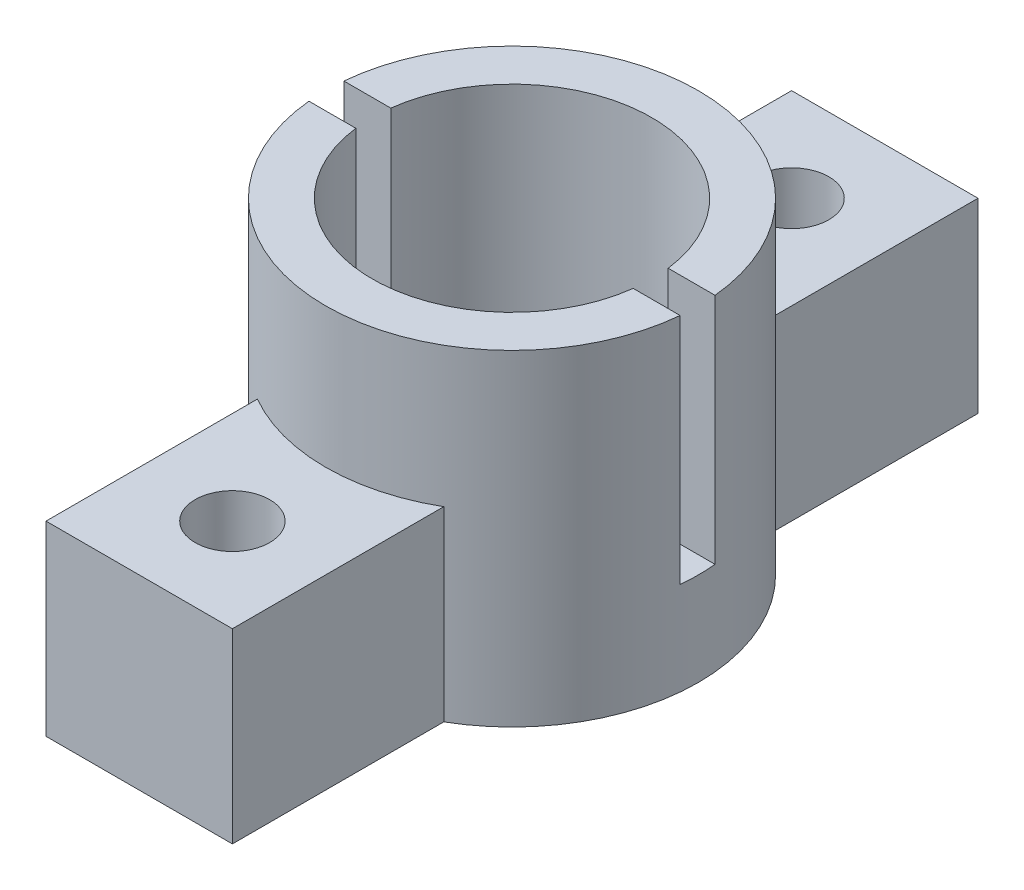
SolidWorks part; units mm, degrees
ref_plane "Plan de face" through (0, 0, 0) normal (0, 0, 1) x (1, 0, 0)
ref_plane "Plan de dessus" through (0, 0, 0) normal (0, 1, 0) x (1, 0, 0)
ref_plane "Plan de droite" through (0, 0, 0) normal (1, 0, 0) x (0, 0, -1)
sketch "Esquisse1" plane through (0, 0, 0) normal (0, 1, 0) x (1, 0, 0)
  circle A0 centre (0, 0) radius 8
  circle A1 centre (0, 0) radius 6
  circle A2 centre (0, 0) radius 2
extrude "Boss.-Extru.1" add sketch "Esquisse1" along normal blind 12 contours A0 A1 region at (-7.7737, 0, 0)
extrude "Boss.-Extru.2" add sketch "Esquisse1<3>" along normal blind 2 contours A1 A2 region at (-5.8303, 0, 0)
sketch "Esquisse1<3>" plane through (0, 0, 0) normal (0, 1, 0) x (1, 0, 0) same geometry as "Esquisse1"
sketch "Esquisse2" plane through (0, 12, 0) normal (0, 1, 0) x (1, 0, 0)
  line L0 (0, 0) -> (8, 0) construction
  line L1 (0, 0) -> (-8, 0) construction
  line L2 (-8, 0) -> (-8, -0.75)
  line L3 (-8, 0) -> (-8, 0.75)
  line L4 (-8, 0.75) -> (-5.9529, 0.75)
  line L5 (-8, -0.75) -> (-5.9529, -0.75)
  line L6 (8, 0) -> (8, -0.75)
  line L7 (8, -0.75) -> (8, 0.75)
  line L8 (8, 0.75) -> (5.9529, 0.75)
  line L9 (8, -0.75) -> (5.9529, -0.75)
  circle A0 centre (0, 0) radius 8 construction
  circle A1 centre (0, 0) radius 6 construction
  circle A2 centre (0, 0) radius 6 construction
  arc A3 (5.9529, 0.75) -> (5.9489, -0.7811) centre (0, 0) cw
  arc A4 (-5.9529, 0.75) -> (-5.9529, -0.75) centre (0, 0) ccw
  circle M5 centre (0, 0) radius 6
  circle M6 centre (0, 0) radius 8
extrude "Enlèv. mat.-Extru.1" cut sketch "Esquisse2" against normal blind 8 contours L5 L4 M6 M5 | L9 L8 M6 M5 region at (-6.9863, 12, 0) region at (6.9863, 12, 0)
sketch "Esquisse3" plane through (0, 0, 0) normal (0, -1, 0) x (1, 0, 0)
  line L0 (0, 0) -> (0, 8) construction
  line L1 (0, 0) -> (0, -8) construction
  line L2 (0, -8) -> (0, -16) construction
  line L3 (0, -16) -> (4, -16)
  line L4 (0, -16) -> (-4, -16)
  line L5 (-4, -16) -> (-4, -6.9282)
  line L6 (4, -16) -> (4, -6.9282)
  line L7 (0, 8) -> (0, 16) construction
  line L8 (0, 16) -> (4, 16)
  line L9 (4, 16) -> (4, 6.9282)
  line L10 (0, 16) -> (-4, 16)
  line L11 (-4, 16) -> (-4, 6.9282)
  line L12 (0, 0) -> (0, -12)
  circle A1 centre (0, 0) radius 8
  circle A2 centre (0, -12) radius 1.6
  circle A3 centre (0, 12) radius 1.6
  circle M1 centre (0, 0) radius 8
  dimension "D1" = 12
extrude "Boss.-Extru.5" add sketch "Esquisse3" against normal blind 8 contours L3 L6 L5 L4 A2 M1 | L10 L11 L9 L8 A3 M1 region at (-2, 0, -15.879) region at (-3.879, 0, 11.4641)
sketch "Esquisse4" plane through (0, 12, 0) normal (0, 1, 0) x (1, 0, 0)
  line L0 (-7.9648, -0.75) -> (-5.9529, -0.75) construction
  line L1 (-7.9648, -0.75) -> (-5.9529, -0.75)
  line L2 (5.9529, -0.75) -> (7.9648, -0.75)
  line L3 (5.9529, 0.75) -> (7.9648, 0.75)
  line L4 (-5.9529, 0.75) -> (-7.9648, 0.75)
  arc A0 (-5.9529, -0.75) -> (5.9529, -0.75) centre (0, 0) ccw
  arc A1 (5.9529, -0.75) -> (5.9529, 0.75) centre (0, 0) ccw construction
  arc A2 (7.9648, -0.75) -> (-7.9648, -0.75) centre (0, 0) cw
  arc A3 (-5.9529, 0.75) -> (5.9529, 0.75) centre (0, 0) cw
  arc A4 (5.9529, 0.75) -> (-5.9529, 0.75) centre (0, 0) ccw construction
  arc A5 (-7.9648, 0.75) -> (7.9648, 0.75) centre (0, 0) cw
  line M1 (-5.9529, -0.75) -> (-7.9648, -0.75)
  arc M2 (-7.9648, -0.75) -> (7.9648, -0.75) centre (0, 0) ccw
  line M3 (7.9648, -0.75) -> (5.9529, -0.75)
  arc M4 (5.9529, -0.75) -> (-5.9529, -0.75) centre (0, 0) cw
extrude "Boss.-Extru.6" add sketch "Esquisse4" along normal blind 2 contours A5 L4 A3 L3 | M4 M1 M2 M3 region at (-6.9589, 12, 0.925) region at (0, 12, -6.175)
